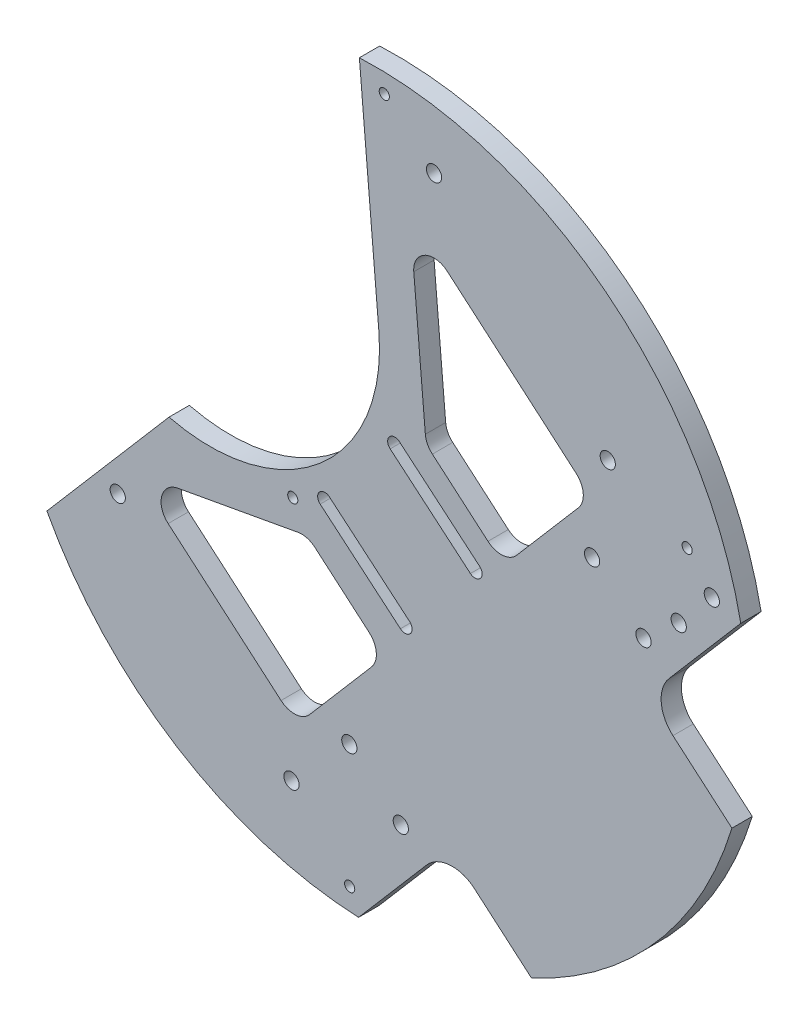
SolidWorks part; units mm, degrees
material "PMMA"
ref_plane "Front Plane" through (0, 0, 0) normal (0, 0, 1) x (1, 0, 0)
ref_plane "Top Plane" through (0, 0, 0) normal (0, 1, 0) x (1, 0, 0)
ref_plane "Right Plane" through (0, 0, 0) normal (1, 0, 0) x (0, 0, -1)
sketch "Sketch1" plane through (0, 0, 0) normal (0, 0, 1) x (1, 0, 0)
  line L0 (-65.0623, 1.7615) -> (-29.0137, 43.7903)
  line L1 (27.1459, 163.7003) -> (32.9106, 96.5808)
  arc A5 (-65.0623, 1.7615) -> (27.1459, 163.7003) centre (31.8495, 53.8009) ccw
  arc A6 (-29.0137, 43.7903) -> (32.9106, 96.5808) centre (-16.906, 92.3022) ccw
  circle A7 centre (-44.1478, 16.6232) radius 2.25
  circle A8 centre (7.1219, -31.0362) radius 2.25
  circle A9 centre (100.4484, 97.5283) radius 2.25
  circle A10 centre (49.1788, 145.1877) radius 2.25
  dimension "D1" = 220
  dimension "D2" = 100
  dimension "D6" = 4.5
  dimension "D3" = 60.8633
  dimension "D4" = 55.3707
  dimension "D5" = 67.1195
extrude "Boss-Extrude1" add sketch "Sketch1" along normal blind 6
sketch "Sketch2" plane through (0, 0, 6) normal (0, 0, 1) x (1, 0, 0)
  line L0 (61.2716, 49.8842) -> (37.5946, 69.8942) construction
  line L1 (59.9161, 48.2803) -> (36.2391, 68.2903)
  line L2 (62.6271, 51.4882) -> (38.9501, 71.4981)
  line L3 (40.6162, 25.4434) -> (16.9392, 45.4534) construction
  line L4 (39.2607, 23.8395) -> (15.5836, 43.8494)
  line L5 (41.9717, 27.0474) -> (18.2947, 47.0573)
  line L6 (61.2716, 49.8842) -> (46.5601, 32.4767) construction
  line L7 (46.5601, 32.4767) -> (37.919, 22.2519) construction
  line L8 (15.0356, 41.8723) -> (37.8103, 22.3451) construction
  line L9 (50.2207, 38.2751) -> (29.803, 55.5304) construction
  line L11 (16.9392, 45.4534) -> (37.5946, 69.8942) construction
  arc A0 (59.9161, 48.2803) -> (62.6271, 51.4882) centre (61.2716, 49.8842) ccw
  arc A1 (38.9501, 71.4981) -> (36.2391, 68.2903) centre (37.5946, 69.8942) ccw
  arc A2 (39.2607, 23.8395) -> (41.9717, 27.0474) centre (40.6162, 25.4434) ccw
  arc A3 (18.2947, 47.0573) -> (15.5836, 43.8494) centre (16.9392, 45.4534) ccw
  circle A5 centre (58.2063, 52.2784) radius 2.25 construction
  point P4 (49.4331, 59.8892)
  point P9 (28.7777, 35.4484)
  dimension "D1" = 4.2
  dimension "D2" = 4.2
  dimension "D3" = 25
  dimension "D4" = 16
  dimension "D5" = 32
  dimension "D6" = 31
  dimension "D7" = 31
  dimension "D8" = 16
extrude "Cut-Extrude1" cut sketch "Sketch2" against normal blind 10
hole_wizard "Ø4.5 (4.5) Diameter Hole" positions "Sketch3" profile "Sketch4" hole size "Ø4.5" standard "IS"
sketch "Sketch3" plane through (207.147, -96.5003, 6) normal (0, 0, 1) x (-0.6509, -0.7592, 0)
  point P0 (80.5001, -194.4616)
  point P3 (77.6909, -264.4052)
  point P6 (-80.6567, -277.2391)
  point P9 (-77.8475, -207.2955)
sketch "Sketch4" plane through (7.1219, -31.0362, 6) normal (1, 0, 0) x (0, -1, 0)
  line L0 (0, 0) -> (0, 11.3519)
  line L1 (0, 11.3519) -> (2.25, 10)
  line L2 (2.25, 10) -> (2.25, 0)
  line L3 (2.25, 0) -> (0, 0)
  line L4 (0, 11.3519) -> (-2.25, 10) construction
  line L5 (0, -6.35) -> (0, 107.95) construction
  dimension "Hole Dia." = 4.5
  dimension "Hole Depth" = 10
  dimension "Drill Angle" = 118
hole_wizard "Ø3.0mm Dowel Hole1" positions "Sketch5" profile "Sketch6" hole size "Ø3.0" standard "IS" end condition through all
sketch "Sketch5" plane through (207.147, -96.5003, 6) normal (0, 0, 1) x (-0.6509, -0.7592, 0)
  point P0 (-80.9158, -296.795)
  point P3 (-84.9452, -182.5189)
  point P6 (25.2163, -241.3641)
  point P9 (83.3286, -169.4245)
sketch "Sketch6" plane through (34.5014, 158.1134, 6) normal (1, 0, 0) x (0, -1, 0)
  line L0 (0, 0) -> (0, 6)
  line L1 (0, 6) -> (1.5, 6)
  line L2 (1.5, 6) -> (1.5, 0)
  line L3 (1.5, 0) -> (0, 0)
  line L4 (0, -6.35) -> (0, 107.95) construction
  dimension "Thru Hole Dia." = 3
  dimension "Thru Hole Depth" = 6
sketch "Sketch7" plane through (0, 0, 6) normal (0, 0, 1) x (1, 0, 0)
  line L0 (139.6991, 75.4449) -> (26.9214, -56.0887) construction
  line L1 (43.1983, 117.032) -> (46.6179, 77.2171)
  line L2 (37.8103, 22.3451) -> (46.2721, 32.2141) construction
  line L3 (139.6991, 75.4449) -> (118.593, 50.8287)
  line L4 (119.6755, 36.7281) -> (137.0907, 21.7962)
  line L5 (84.7078, 70.4904) -> (146.9639, 12.6182) construction
  line L6 (137.0907, 21.7962) -> (157.1753, 45.221)
  line L7 (157.1753, 45.221) -> (139.6991, 75.4449)
  line L8 (26.9214, -56.0887) -> (46.9652, -32.7114)
  line L9 (61.0658, -31.6289) -> (77.9252, -46.0842)
  line L10 (23.4315, 4.5722) -> (85.6875, -53.2999) construction
  line L11 (77.9252, -46.0842) -> (19.3436, -114.4084)
  line L12 (19.3436, -114.4084) -> (26.9214, -56.0887)
  line L13 (39.3736, -26.2023) -> (111.0015, 57.3378) construction
  line L14 (111.0015, 57.3378) -> (95.8183, 70.3559) construction
  line L15 (95.8183, 70.3559) -> (24.1905, -13.1842) construction
  line L16 (24.1905, -13.1842) -> (39.3736, -26.2023) construction
  line L17 (121.3911, 66.3826) -> (131.1547, 77.77) construction
  line L22 (48.6904, 73.1756) -> (65.098, 59.1076)
  line L23 (73.5583, 59.7571) -> (91.7837, 81.0135)
  line L24 (91.1342, 89.4739) -> (53.0817, 122.1004)
  line L26 (27.1459, 163.7003) -> (32.9106, 96.5808) construction
  line L28 (97.3021, 86.7998) -> (87.7806, 95.6509) construction
  line L29 (30.0709, 18.2552) -> (14.02, 32.0174)
  line L30 (9.0403, 33.3655) -> (-26.4449, 26.9077)
  line L31 (-29.2761, 16.4497) -> (4.0346, -12.1111)
  line L32 (12.495, -11.4616) -> (30.7204, 9.7948)
  line L33 (17.5925, -27.1162) -> (8.071, -18.2652) construction
  line L35 (-29.0137, 43.7903) -> (-65.0623, 1.7615) construction
  arc A0 (-65.0623, 1.7615) -> (27.1459, 163.7003) centre (31.8495, 53.8009) ccw construction
  arc A1 (65.098, 59.1076) -> (73.5583, 59.7571) centre (69.0034, 63.6626) ccw
  circle A2 centre (34.5014, 158.1134) radius 1.6 construction
  arc A3 (118.593, 50.8287) -> (119.6755, 36.7281) centre (126.1846, 44.3196) ccw
  arc A4 (46.9652, -32.7114) -> (61.0658, -31.6289) centre (54.5568, -39.2205) cw
  circle A5 centre (39.3736, -26.2023) radius 2.25
  circle A6 centre (111.0015, 57.3378) radius 2.25
  circle A7 centre (24.1905, -13.1842) radius 2.25
  circle A8 centre (95.8183, 70.3559) radius 2.25
  circle A9 centre (121.3911, 66.3826) radius 2.25
  circle A10 centre (131.1547, 77.77) radius 2.25
  arc A11 (46.6179, 77.2171) -> (48.6904, 73.1756) centre (52.5958, 77.7305) ccw
  arc A12 (43.1983, 117.032) -> (53.0817, 122.1004) centre (49.1763, 117.5455) cw
  arc A13 (91.7837, 81.0135) -> (91.1342, 89.4739) centre (87.2288, 84.919) ccw
  arc A14 (14.02, 32.0174) -> (9.0403, 33.3655) centre (10.1145, 27.4624) ccw
  arc A15 (30.0709, 18.2552) -> (30.7204, 9.7948) centre (26.1654, 13.7003) cw
  arc A16 (4.0346, -12.1111) -> (12.495, -11.4616) centre (7.94, -7.5561) ccw
  arc A17 (-26.4449, 26.9077) -> (-29.2761, 16.4497) centre (-25.3706, 21.0046) ccw
  point P22 (112.084, 43.2371)
  point P25 (53.4743, -25.1198)
  point P55 (69.6529, 55.2022)
  point P62 (95.6892, 85.5685)
  point P65 (11.8511, 33.877)
  point P68 (34.6258, 14.3498)
  point P71 (8.5895, -16.0165)
  point P74 (-38.842, 24.6516)
  dimension "D8" = 10
  dimension "D9" = 4.5
  dimension "D26" = 6
  dimension "D1" = 214.3362
  dimension "D2" = 90
  dimension "D3" = 90
  dimension "D4" = 90
  dimension "D5" = 30.8563
  dimension "D6" = 90
  dimension "D7" = 90
  dimension "D10" = 20
  dimension "D11" = 10
  dimension "D12" = 10
  dimension "D13" = 10
  dimension "D14" = 8
  dimension "D15" = 15
  dimension "D16" = 15.5539
  dimension "D17" = 12
  dimension "D18" = 2
  dimension "D19" = 40
  dimension "D20" = 40
  dimension "D21" = 40
  dimension "D22" = 2
  dimension "D23" = 40
  dimension "D24" = 5
  dimension "D25" = 30
extrude "Cut-Extrude2" cut sketch "Sketch7" against normal blind 10
